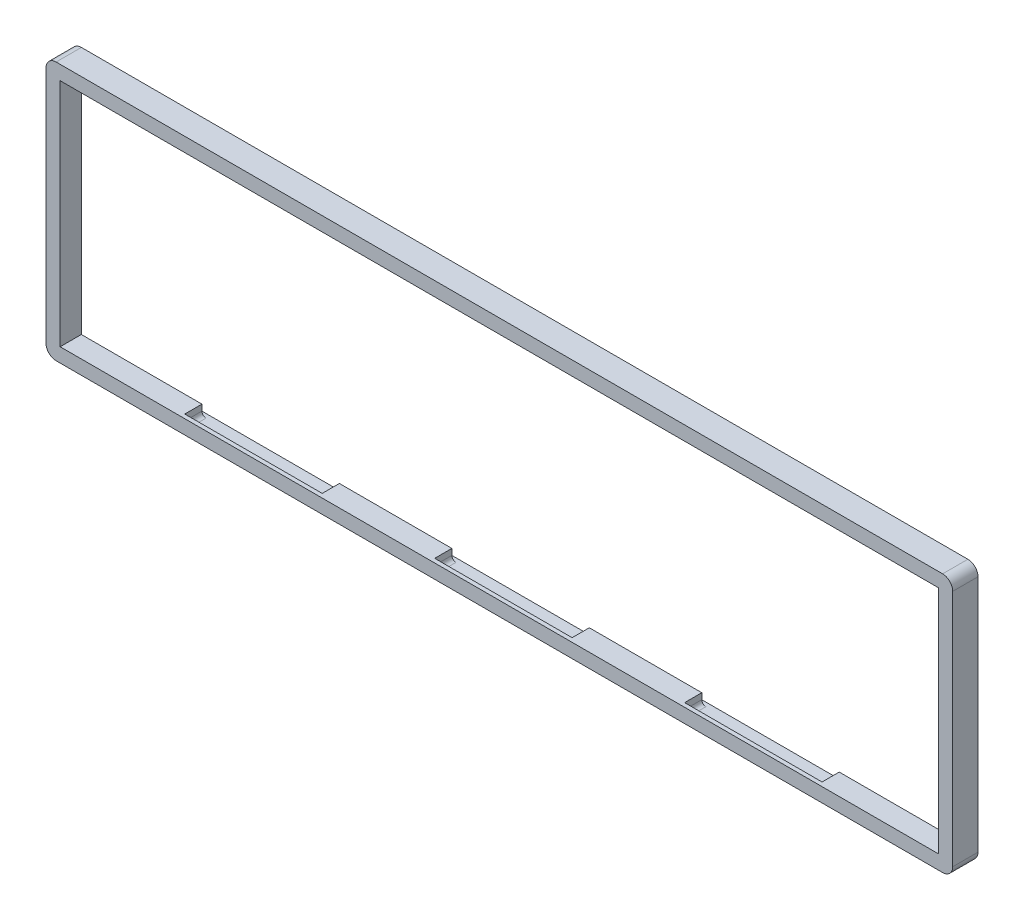
SolidWorks part; units mm, degrees
ref_plane "Front Plane" through (0, 0, 0) normal (0, 0, 1) x (1, 0, 0)
ref_plane "Top Plane" through (0, 0, 0) normal (0, 1, 0) x (1, 0, 0)
ref_plane "Right Plane" through (0, 0, 0) normal (1, 0, 0) x (0, 0, -1)
sketch "Sketch1" plane through (0, 0, 0) normal (0, 0, 1) x (1, 0, 0)
  line L0 (306.936, 114) -> (374.936, 114)
  line L1 (0, 0) -> (434.581, 0)
  line L2 (0, 0) -> (0, 114)
  line L3 (0, 114) -> (434.581, 114)
  line L4 (434.581, 0) -> (434.581, 114)
  line L5 (-2, -7) -> (436.581, -7)
  line L6 (-7, -2) -> (-7, 116)
  line L7 (-2, 121) -> (436.581, 121)
  line L8 (441.581, -2) -> (441.581, 116)
  line L9 (374.936, 114) -> (306.936, 114)
  line L10 (374.936, 114) -> (374.936, 117)
  line L11 (372.936, 119) -> (308.936, 119)
  line L12 (306.936, 114) -> (306.936, 117)
  line L13 (183.291, 114) -> (251.291, 114)
  line L14 (251.291, 114) -> (183.291, 114)
  line L15 (251.291, 114) -> (251.291, 117)
  line L16 (249.291, 119) -> (185.291, 119)
  line L17 (183.291, 114) -> (183.291, 117)
  line L18 (59.646, 0) -> (127.646, 0)
  line L19 (59.646, 0) -> (127.646, 0)
  line L20 (59.646, 0) -> (59.646, -3)
  line L21 (61.646, -5) -> (125.646, -5)
  line L22 (127.646, 0) -> (127.646, -3)
  line L23 (59.646, 114) -> (127.646, 114)
  line L24 (127.646, 114) -> (59.646, 114)
  line L25 (127.646, 114) -> (127.646, 117)
  line L26 (125.646, 119) -> (61.646, 119)
  line L27 (59.646, 114) -> (59.646, 117)
  line L29 (183.291, 0) -> (251.291, 0)
  line L30 (183.291, 0) -> (183.291, -3)
  line L31 (185.291, -5) -> (249.291, -5)
  line L32 (251.291, 0) -> (251.291, -3)
  line L33 (306.936, 0) -> (374.936, 0)
  line L34 (306.936, 0) -> (306.936, -3)
  line L35 (308.936, -5) -> (372.936, -5)
  line L36 (374.936, 0) -> (374.936, -3)
  arc A0 (372.936, 119) -> (374.936, 117) centre (372.936, 117) cw
  arc A1 (308.936, 119) -> (306.936, 117) centre (308.936, 117) ccw
  arc A2 (249.291, 119) -> (251.291, 117) centre (249.291, 117) cw
  arc A3 (185.291, 119) -> (183.291, 117) centre (185.291, 117) ccw
  arc A4 (125.646, -5) -> (127.646, -3) centre (125.646, -3) ccw
  arc A5 (61.646, -5) -> (59.646, -3) centre (61.646, -3) cw
  arc A6 (125.646, 119) -> (127.646, 117) centre (125.646, 117) cw
  arc A7 (61.646, 119) -> (59.646, 117) centre (61.646, 117) ccw
  arc A8 (249.291, -5) -> (251.291, -3) centre (249.291, -3) ccw
  arc A9 (183.291, -3) -> (185.291, -5) centre (185.291, -3) ccw
  arc A10 (372.936, -5) -> (374.936, -3) centre (372.936, -3) ccw
  arc A11 (306.936, -3) -> (308.936, -5) centre (308.936, -3) ccw
  arc A12 (-2, -7) -> (-7, -2) centre (-2, -2) cw
  arc A13 (436.581, -7) -> (441.581, -2) centre (436.581, -2) ccw
  arc A14 (436.581, 121) -> (441.581, 116) centre (436.581, 116) cw
  arc A15 (-7, 116) -> (-2, 121) centre (-2, 116) cw
  point P15 (374.936, 119)
  point P18 (306.936, 119)
  point P33 (127.646, -5)
  point P44 (59.646, -5)
  dimension "D10" = 2
  dimension "D19" = 2
  dimension "D20" = 2
  dimension "D21" = 2
  dimension "D22" = 5
  dimension "D1" = 434.581
  dimension "D2" = 114
  dimension "D3" = 7
  dimension "D4" = 7
  dimension "D5" = 7
  dimension "D6" = 7
  dimension "D7" = 68
  dimension "D8" = 59.645
  dimension "D9" = 5
  dimension "D11" = 0
  dimension "D12" = 55.645
  dimension "D13" = 55.645
  dimension "D14" = 0
  dimension "D15" = 5
  dimension "D16" = 5
  dimension "D17" = 68
  dimension "D18" = 5
extrude "Boss-Extrude1" add sketch "Sketch1" along normal blind 12.5 contours A15 L6 A12 L5 A13 L8 A14 L7 A11 L34 L1 L32 A8 L31 A9 L30 L22 A4 L21 A5 L20 L2 L3 L27 A7 L26 A6 L25 L17 A3 L16 A2 L15 L12 A1 L11 A0 L10 L4 L36 A10 L35 region at (-2.237, -2.237, 0)
sketch "Sketch2" plane through (0, 0, 12.5) normal (0, 0, 1) x (1, 0, 0)
  line L0 (374.936, 0) -> (434.581, 0) construction
  line L1 (-2, 121) -> (436.581, 121)
  line L2 (-2, 121) -> (-2, -7)
  line L3 (-2, -7) -> (436.581, -7)
  line L4 (436.581, 121) -> (436.581, -7)
  line L5 (0, 114) -> (434.581, 114)
  line L6 (0, 114) -> (0, 0)
  line L7 (0, 0) -> (434.581, 0)
  line L8 (434.581, 114) -> (434.581, 0)
  line L9 (434.581, 0) -> (434.581, 114) construction
extrude "Boss-Extrude2" add sketch "Sketch2" against normal blind 2
sketch "Sketch3" plane through (0, 0, 0) normal (0, 0, -1) x (-1, 0, 0)
  line L0 (-372.936, 119) -> (-308.936, 119) construction
  line L1 (-437.581, 119) -> (3.0013, 119)
  line L2 (-437.581, 119) -> (-437.581, -5)
  line L3 (-437.581, -5) -> (3.0013, -5)
  line L4 (3.0013, 119) -> (3.0013, -5)
  line L5 (-434.581, 0) -> (-434.581, 114) construction
  line L6 (0, 0) -> (0, 114) construction
  line L7 (0, 0) -> (-59.646, 0) construction
  dimension "D1" = 0
  dimension "D2" = 3
  dimension "D3" = 3.0013
  dimension "D4" = 5
extrude "Cut-Extrude1" cut sketch "Sketch3" against normal blind 2
